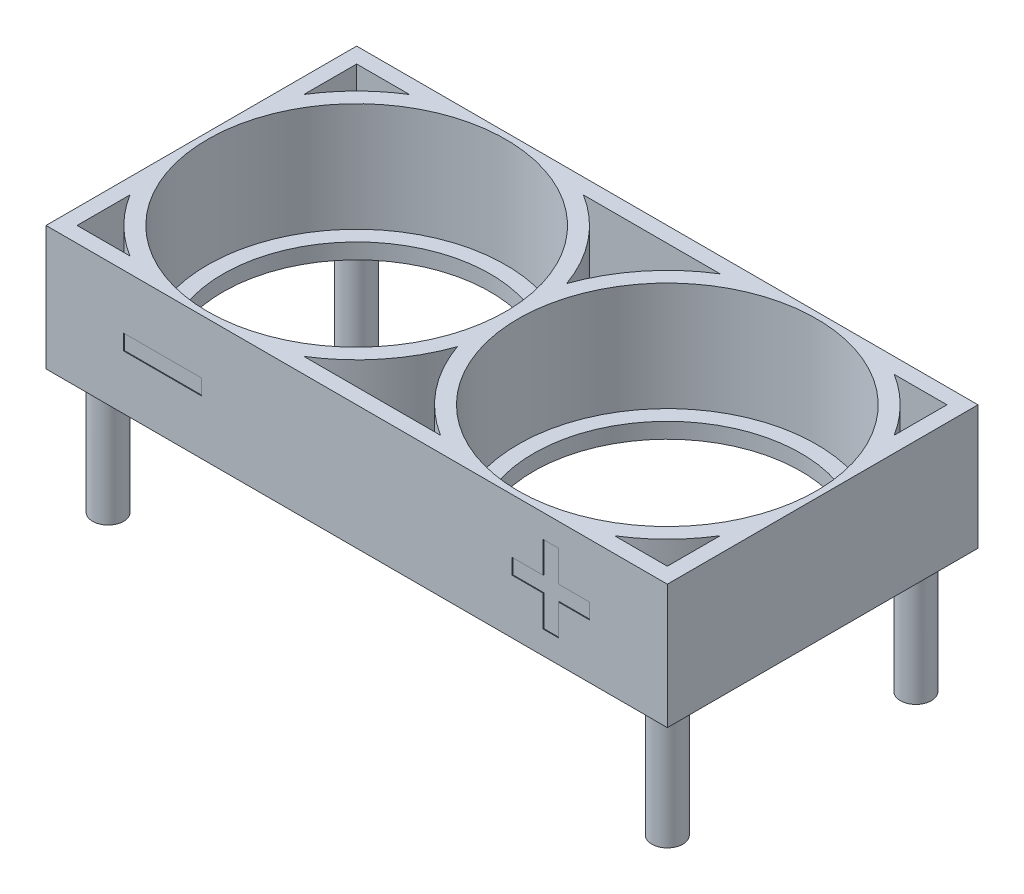
SolidWorks part; units mm, degrees
material "PP homopolimer"
ref_plane "Płaszczyzna przednia" through (0, 0, 0) normal (0, 0, 1) x (1, 0, 0)
ref_plane "Płaszczyzna górna" through (0, 0, 0) normal (0, 1, 0) x (1, 0, 0)
ref_plane "Płaszczyzna prawa" through (0, 0, 0) normal (1, 0, 0) x (0, 0, -1)
sketch "Szkic1" plane through (0, 0, 0) normal (0, 1, 0) x (1, 0, 0)
  line L1 (40, -20) -> (-40, -20)
  line L2 (40, -20) -> (40, 20)
  line L3 (40, 20) -> (-40, 20)
  line L4 (-40, -20) -> (-40, 20)
  line L5 (40, -20) -> (-40, 20) construction
  line L6 (40, 20) -> (-40, -20) construction
  point P0 (0, 0)
  dimension "D1" = 80
  dimension "D2" = 40
extrude "Dodanie-wyciągnięcie1" add sketch "Szkic1" along normal blind 16
sketch "Szkic2" plane through (0, 16, 0) normal (0, 1, 0) x (1, 0, 0)
  line L0 (-20, 0) -> (20, 0) construction
  circle A0 centre (-20, 0) radius 19.2
  circle A1 centre (20, 0) radius 19.2
  dimension "D2" = 38.4
  dimension "D1" = 40
extrude "Wytnij-wyciągnięcie1" cut sketch "Szkic2" against normal offset from surface (14 mm away) 2 up to face at (0, 0, 0)
sketch "Szkic3" plane through (0, 2, 0) normal (0, 1, 0) x (1, 0, 0)
  circle A0 centre (-20, 0) radius 17.2
  circle A1 centre (20, 0) radius 17.2
  circle A2 centre (-20, 0) radius 19.2 construction
  dimension "D1" = 2
extrude "Wytnij-wyciągnięcie2" cut sketch "Szkic3" against normal up to next
sketch "Szkic4" plane through (0, 16, 0) normal (0, 1, 0) x (1, 0, 0)
  line L0 (-38, 11.2) -> (-38, 18)
  line L1 (-38, 18) -> (-31.2, 18)
  line L2 (40, 20) -> (-40, 20) construction
  line L3 (-40, 20) -> (-40, -20) construction
  line L4 (-8.8, 18) -> (8.8, 18)
  line L5 (31.2, 18) -> (38, 18)
  line L6 (38, 18) -> (38, 11.2)
  line L7 (38, -11.2) -> (38, -18)
  line L8 (38, -18) -> (31.2, -18)
  line L9 (8.8, -18) -> (-8.8, -18)
  line L10 (-31.2, -18) -> (-38, -18)
  line L11 (-38, -18) -> (-38, -11.2)
  arc A0 (-38, 11.2) -> (-31.2, 18) centre (-20, 0) cw
  circle A1 centre (-20, 0) radius 19.2 construction
  circle A2 centre (-20, 0) radius 19.2 construction
  arc A3 (-8.8, 18) -> (0, 7.0314) centre (-20, 0) cw
  arc A4 (0, 7.0314) -> (8.8, 18) centre (20, 0) cw
  circle A5 centre (20, 0) radius 19.2 construction
  arc A6 (31.2, 18) -> (38, 11.2) centre (20, 0) cw
  circle A7 centre (20, 0) radius 19.2 construction
  arc A8 (38, -11.2) -> (31.2, -18) centre (20, 0) cw
  arc A9 (-38, -11.2) -> (-31.2, -18) centre (-20, 0) ccw
  arc A10 (-8.8, -18) -> (0, -7.0314) centre (-20, 0) ccw
  arc A11 (0, -7.0314) -> (8.8, -18) centre (20, 0) ccw
  dimension "D3" = 2
  dimension "D1" = 2
  dimension "D2" = 2
extrude "Wytnij-wyciągnięcie3" cut sketch "Szkic4" against normal up to surface (14 mm away) up to face at (-20, 2, 17.2)
sketch "Szkic5" plane through (0, 0, 0) normal (0, -1, 0) x (1, 0, 0)
  line L0 (36, 16) -> (-36, 16) construction
  line L1 (-36, 16) -> (-36, -16) construction
  line L2 (-36, -16) -> (36, -16) construction
  line L3 (36, -16) -> (36, 16) construction
  circle A0 centre (36, 16) radius 2
  circle A1 centre (36, -16) radius 2
  circle A2 centre (-36, -16) radius 2
  circle A3 centre (-36, 16) radius 2
  point P8 (0, 16)
  point P9 (36, 0)
  dimension "D1" = 4
  dimension "D2" = 72
  dimension "D3" = 32
extrude "Dodanie-wyciągnięcie2" add sketch "Szkic5" along normal blind 16
sketch "Szkic6" plane through (0, 0, -20) normal (0, 0, -1) x (-1, 0, 0)
  line L0 (-25, 13) -> (-25, 3) construction
  line L1 (-30, 8) -> (-20, 8) construction
  line L2 (-40, 16) -> (-40, 0) construction
  line L3 (-30, 7) -> (-26, 7)
  line L4 (-26, 13) -> (-26, 9)
  line L5 (-30, 9) -> (-26, 9)
  line L6 (-24, 13) -> (-24, 9)
  line L7 (-30, 7) -> (-30, 9)
  line L8 (-20, 7) -> (-20, 9)
  line L9 (-26, 13) -> (-24, 13)
  line L10 (-26, 3) -> (-24, 3)
  line L11 (-24, 7) -> (-20, 7)
  line L12 (-30, 7) -> (-20, 7) construction
  line L13 (-26, 7) -> (-26, 3)
  line L14 (-26, 13) -> (-26, 3) construction
  line L15 (-24, 9) -> (-20, 9)
  line L16 (-30, 9) -> (-20, 9) construction
  line L17 (-24, 7) -> (-24, 3)
  line L18 (-24, 13) -> (-24, 3) construction
  line L20 (30, 7) -> (20, 7)
  line L21 (30, 7) -> (30, 9)
  line L22 (30, 9) -> (20, 9)
  line L23 (20, 7) -> (20, 9)
  line L24 (30, 7) -> (20, 9) construction
  line L25 (30, 9) -> (20, 7) construction
  point P4 (-25, 8)
  point P7 (-40, 8)
  point P18 (25, 8)
  dimension "D1" = 10
  dimension "D2" = 25
  dimension "D5" = 10
  dimension "D6" = 25
  dimension "D3" = 1
  dimension "D4" = 1
extrude "Wytnij-wyciągnięcie4" cut sketch "Szkic6" against normal blind 0.1
mirror "Lustro1" about plane through (0, 0, 0) normal (0, 0, 1) of "Wytnij-wyciągnięcie4"
sketch "Szkic7" plane through (0, 0, 0) normal (0, -1, 0) x (1, 0, 0)
  line L0 (31, 19) -> (31, 15) construction
  line L1 (29, 17) -> (33, 17) construction
  line L2 (30.5, 19) -> (30.5, 17.5)
  line L3 (29, 16.5) -> (30.5, 16.5)
  line L4 (31.5, 19) -> (31.5, 17.5)
  line L5 (29, 17.5) -> (30.5, 17.5)
  line L6 (30.5, 19) -> (31.5, 19)
  line L7 (30.5, 15) -> (31.5, 15)
  line L8 (29, 16.5) -> (29, 17.5)
  line L9 (33, 16.5) -> (33, 17.5)
  line L10 (30.5, 16.5) -> (30.5, 15)
  line L11 (30.5, 19) -> (30.5, 15) construction
  line L12 (31.5, 17.5) -> (33, 17.5)
  line L13 (29, 17.5) -> (33, 17.5) construction
  line L14 (31.5, 16.5) -> (31.5, 15)
  line L15 (31.5, 19) -> (31.5, 15) construction
  line L16 (31.5, 16.5) -> (33, 16.5)
  line L17 (29, 16.5) -> (33, 16.5) construction
  line L19 (-33, -17.5) -> (-29, -17.5)
  line L20 (-33, -17.5) -> (-33, -16.5)
  line L21 (-33, -16.5) -> (-29, -16.5)
  line L22 (-29, -17.5) -> (-29, -16.5)
  line L23 (-33, -17.5) -> (-29, -16.5) construction
  line L24 (-33, -16.5) -> (-29, -17.5) construction
  point P5 (31, 17)
  point P6 (31, 17)
  point P18 (-31, -17)
  dimension "D1" = 4
  dimension "D2" = 31
  dimension "D3" = 17
  dimension "D6" = 1
  dimension "D7" = 4
  dimension "D8" = 31
  dimension "D9" = 17
  dimension "D4" = 0.5
  dimension "D5" = 0.5
extrude "Wytnij-wyciągnięcie5" cut sketch "Szkic7" against normal blind 0.1
